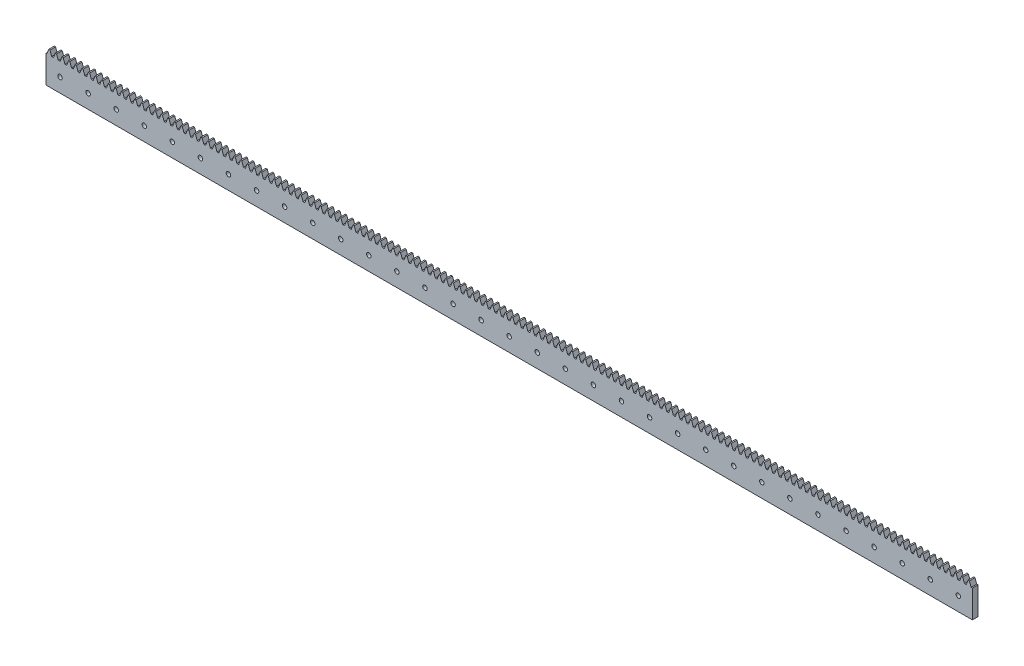
SolidWorks part; units mm, degrees
extrude "Blank" add sketch "BlankSke" against normal blind 4
sketch "BlankSke" plane through (0, 0, 0) normal (0, 0, 1) x (1, 0, 0)
  line L1 (0, 0) -> (660, 0)
  line L2 (0, 0) -> (0, 23)
  line L3 (0, 23) -> (660, 23)
  line L4 (660, 0) -> (660, 23)
  dimension "Length" = 660
ref_plane "Plane1" through (0, 0, 0) normal (0, 0, 1) x (1, 0, 0)
ref_plane "Plane2" through (0, 0, 0) normal (0, 1, 0) x (1, 0, 0)
ref_plane "Plane3" through (0, 0, 0) normal (1, 0, 0) x (0, 0, -1)
other "Configuration Table"
sketch "HoldingSke" plane through (0, 0, 0) normal (0, 1, 0) x (1, 0, 0)
  line L0 (0, 0) -> (0.0928, 0.6602)
  line L1 (-15, 0) -> (100, 0) construction
  line L2 (0, 0) -> (-2.1039, 2.3779)
  line L3 (0, 0) -> (-11.863, 4.5341)
  line L4 (0, 0) -> (-6.8053, 5.3169)
  line L5 (0, 0) -> (-23.7986, -8.8762)
  line L6 (0, 0) -> (-10.5278, -7.1032)
  line L9 (-71.009, 38.7566) -> (549.1882, 264.4899)
  line L10 (-76.2, 3.8779) -> (-54.7, 3.8779)
  line L11 (0, 0) -> (-4, 0)
  line L12 (-76.2, 101.6) -> (-76.147, 101.6)
  line L13 (24.9733, 27.94) -> (52.9518, 28.4284)
  line L14 (24.9733, 27.94) -> (24.9743, 27.94)
  line L15 (24.9733, 27.94) -> (100.4006, 29.5858)
  circle A0 centre (0, 0) radius 19.05
  circle A1 centre (0, 0) radius 10.75
  circle A2 centre (0, 0) radius 12.7
  dimension "Num_teeth" = 142
  dimension "Width" = 4
  dimension "Length" = 660
  dimension "Pitch_height" = 21.5
sketch "TooCutSkeIll" plane through (0, 0, 0) normal (0, 0, 1) x (1, 0, 0)
  line L0 (-1.8687, 22.9605) -> (-0.7447, 19.8724)
  line L1 (-0.3914, 19.625) -> (0.3914, 19.625)
  line L2 (0.7447, 19.8724) -> (1.8687, 22.9605)
  line L3 (660, 23) -> (0, 23) construction
  line L4 (0, 0) -> (0, 64.897) construction
  line L5 (-13.208, 21.5) -> (12.954, 21.5) construction
  line L6 (0, 0) -> (660, 0) construction
  line L7 (1.3371, 21.5) -> (1.3371, 48.7463) construction
  line L8 (-1.3371, 21.5) -> (-1.3371, 48.7463) construction
  line L9 (1.9251, 23) -> (1.9251, 23.0254)
  line L10 (-1.9251, 23) -> (-1.9251, 23.0254)
  line L11 (-1.9251, 23.0254) -> (1.9251, 23.0254)
  arc A0 (0.3914, 19.625) -> (0.7447, 19.8724) centre (0.3914, 20.001) ccw
  arc A1 (-0.7447, 19.8724) -> (-0.3914, 19.625) centre (-0.3914, 20.001) ccw
  arc A2 (1.9251, 23) -> (1.8687, 22.9605) centre (1.9251, 22.94) ccw
  arc A3 (-1.8687, 22.9605) -> (-1.9251, 23) centre (-1.9251, 22.94) ccw
  dimension "Addendum_plus" = 1.5254
  dimension "Pitch_height" = 21.5
  dimension "Pressure_angle" = 20
  dimension "Gap_width" = 2.6742
  dimension "Dedendum" = 1.875
extrude "ToothCutIll" [suppressed] cut sketch "TooCutSkeIll" against normal through all
sketch "TooCutSkeSim" plane through (0, 0, 0) normal (0, 0, 1) x (1, 0, 0)
  line L0 (0.6547, 19.625) -> (-0.6547, 19.625)
  line L1 (1.8923, 23.0254) -> (0.6547, 19.625)
  line L2 (0, 17.4625) -> (0, 53.467) construction
  line L3 (1.8923, 23.0254) -> (-1.8923, 23.0254)
  line L6 (-1.8923, 23.0254) -> (-0.6547, 19.625)
  line L9 (-1.3371, 21.5) -> (1.3371, 21.5) construction
  line L10 (0, 0) -> (660, 0) construction
  line L11 (1.3371, 21.5) -> (1.3371, 53.467) construction
  line L12 (-1.3371, 21.5) -> (-1.3371, 53.467) construction
  dimension "Addendum_plus" = 1.5254
  dimension "Pitch_height" = 21.5
  dimension "Pressure_angle" = 20
  dimension "Gap_width" = 2.6742
  dimension "Dedendum" = 1.875
extrude "ToothCutSim" cut sketch "TooCutSkeSim" against normal through all
pattern_linear "TeethCuts" count 142 spacing 4.7124 along (1, 0, 0) of "ToothCutIll", "ToothCutSim"
sketch "草图1" plane through (0, 0, -4) normal (0, 0, -1) x (-1, 0, 0)
  line L0 (-660, 10) -> (0, 10) construction
  line L1 (-660, 0) -> (-660, 19.625) construction
  line L2 (0, 19.625) -> (0, 0) construction
  line L3 (0, 0) -> (-660, 0) construction
  circle A0 centre (-650, 10) radius 1.6
  circle A1 centre (-630, 10) radius 1.6
  circle A2 centre (-610, 10) radius 1.6
  circle A3 centre (-590, 10) radius 1.6
  circle A4 centre (-570, 10) radius 1.6
  circle A5 centre (-550, 10) radius 1.6
  circle A6 centre (-530, 10) radius 1.6
  circle A7 centre (-510, 10) radius 1.6
  circle A8 centre (-490, 10) radius 1.6
  circle A9 centre (-470, 10) radius 1.6
  circle A10 centre (-450, 10) radius 1.6
  circle A11 centre (-430, 10) radius 1.6
  circle A12 centre (-410, 10) radius 1.6
  circle A13 centre (-390, 10) radius 1.6
  circle A14 centre (-370, 10) radius 1.6
  circle A15 centre (-350, 10) radius 1.6
  circle A16 centre (-330, 10) radius 1.6
  circle A17 centre (-310, 10) radius 1.6
  circle A18 centre (-290, 10) radius 1.6
  circle A19 centre (-270, 10) radius 1.6
  circle A20 centre (-250, 10) radius 1.6
  circle A21 centre (-230, 10) radius 1.6
  circle A22 centre (-210, 10) radius 1.6
  circle A23 centre (-190, 10) radius 1.6
  circle A24 centre (-170, 10) radius 1.6
  circle A25 centre (-150, 10) radius 1.6
  circle A26 centre (-130, 10) radius 1.6
  circle A27 centre (-110, 10) radius 1.6
  circle A28 centre (-90, 10) radius 1.6
  circle A29 centre (-70, 10) radius 1.6
  circle A30 centre (-50, 10) radius 1.6
  circle A31 centre (-30, 10) radius 1.6
  circle A32 centre (-10, 10) radius 1.6
  dimension "D2" = 3.2
  dimension "D1" = 10
  dimension "D3" = 10
  dimension "D5" = 20
  dimension "D4" = 33
extrude "切除-拉伸1" cut sketch "草图1" against normal through all
equation "' \"Module@HoldingSke\" = 6.35"
equation "' \"Num_teeth@HoldingSke\" = 12"
equation "' \"Ap@HoldingSke\" =  20"
equation "' \"Ap@HoldingSke\" = 20"
equation "' \"Width@HoldingSke\" = 0.25 * 25.4"
equation "' \"Show_teeth@HoldingSke\" = 500"
equation "' \"Backlash@HoldingSke\" = 0.009 * 25.4"
equation "' \"Addendum_fac@HoldingSke\" = 1.0"
equation "' \"Dedendum_fac@HoldingSke\" = 1.25"
equation "' \"Dedendum_add@HoldingSke\" = 0.00005 * 25.4"
equation "' \"Clearance_fac@HoldingSke\" = 0.25"
equation "' \"Pitch_height@HoldingSke\" = 1 * 25.4"
equation "' \"Length@HoldingSke\" = 4.71 * 25.4"
equation "\"Pitch@HoldingSke\" = 1 / \"Module@HoldingSke\""
equation "\"MPH@HoldingSke\" = \"Dedendum_fac@HoldingSke\" / \"Pitch@HoldingSke\" + 2 * \"Dedendum_add@HoldingSke\" + 0.002 * 25.4"
equation "\"MPH@HoldingSke\" = ((sgn( \"MPH@HoldingSke\" - \"Pitch_height@HoldingSke\")+1)*( \"MPH@HoldingSke\" - \"Pitch_height@HoldingSke\"))/2 + \"Pitch_height@HoldingSke\""
equation "\"Blank_height@BlankSke\" = \"Pitch_height@HoldingSke\" + \"Addendum_fac@HoldingSke\"  / \"Pitch@HoldingSke\" "
equation "\"Length@BlankSke\" =  \"Length@HoldingSke\""
equation "\"Face_width@Blank\" = \"Width@HoldingSke\""
equation "\"Pressure_angle@TooCutSkeIll\" = \"Ap@HoldingSke\""
equation "\"Addendum_plus@TooCutSkeIll\" =  \"Addendum_fac@HoldingSke\"  / \"Pitch@HoldingSke\" + 0.001 *25.4"
equation "\"Dedendum@TooCutSkeIll\" = \"Dedendum_fac@HoldingSke\"  / \"Pitch@HoldingSke\""
equation "\"Pitch_height@TooCutSkeIll\" =  \"MPH@HoldingSke\""
equation "\"Gap_width@TooCutSkeIll\" = 3.14159265 / 2 / \"Pitch@HoldingSke\" + 6 * \"Backlash@HoldingSke\""
equation "\"Pressure_angle@TooCutSkeSim\" = \"Ap@HoldingSke\""
equation "\"Addendum_plus@TooCutSkeSim\" =  \"Addendum_fac@HoldingSke\"  / \"Pitch@HoldingSke\" + 0.001 * 25.4"
equation "\"Dedendum@TooCutSkeSim\" = \"Dedendum_fac@HoldingSke\"  / \"Pitch@HoldingSke\""
equation "\"Pitch_height@TooCutSkeSim\" =  \"MPH@HoldingSke\""
equation "\"Gap_width@TooCutSkeSim\" = 3.14159265 / 2 / \"Pitch@HoldingSke\" + 6 * \"Backlash@HoldingSke\""
equation "\"Root_fillet@TooCutSkeIll\" = \"Clearance_fac@HoldingSke\" / \"Pitch@HoldingSke\" + \"Dedendum_add@HoldingSke\""
equation "\"Break_rad@TooCutSkeIll\" = 0.02 / \"Pitch@HoldingSke\" * 2"
equation "\"Linear_pitch@TeethCuts\" = 3.14159265 / \"Pitch@HoldingSke\""
equation "\"Num_teeth@HoldingSke\" = int( ( \"Length@HoldingSke\" + 0 ) / (3.14159265 / \"Pitch@HoldingSke\")) + 0.9999  + 1"
equation " \"Num_teeth@TeethCuts\" = int( \"Show_teeth@HoldingSke\" ) + 1"
equation " \"Num_teeth@TeethCuts\" = ((sgn( \"Num_teeth@TeethCuts\" - \"Num_teeth@HoldingSke\" )-1)*( \"Num_teeth@TeethCuts\" - \"Num_teeth@HoldingSke\" ))/-2+ \"Num_teeth@HoldingSke\""
equation " \"Num_teeth@TeethCuts\" = ((sgn( \"Num_teeth@TeethCuts\" - 2.0)+1)*( \"Num_teeth@TeethCuts\" - 2.0))/2 +2.0"
